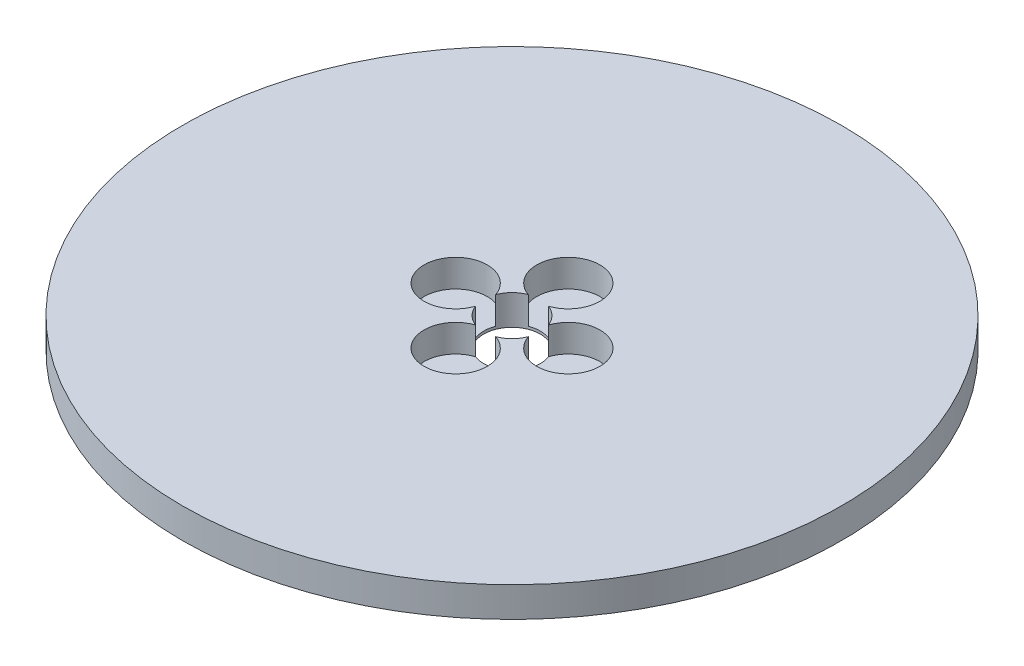
SolidWorks part; units mm, degrees
ref_plane "Front Plane" through (0, 0, 0) normal (0, 0, 1) x (1, 0, 0)
ref_plane "Top Plane" through (0, 0, 0) normal (0, 1, 0) x (1, 0, 0)
ref_plane "Right Plane" through (0, 0, 0) normal (1, 0, 0) x (0, 0, -1)
sketch "Sketch1" plane through (0, 0, 0) normal (0, 1, 0) x (1, 0, 0)
  circle A0 centre (0, 0) radius 87.5
  dimension "FLANGE_OD" = 175
extrude "Boss-Extrude1" add sketch "Sketch1" along normal blind 8
sketch "Sketch2" plane through (0, 0, 0) normal (0, 1, 0) x (1, 0, 0)
  circle A0 centre (0, 0) radius 7.5
  dimension "BORE_D" = 15
extrude "Cut-Extrude1" cut sketch "Sketch2" along normal through all
sketch "Sketch3" plane through (0, 8, 0) normal (0, 1, 0) x (1, 0, 0)
  circle A0 centre (0, 0) radius 14.9537 construction
  circle A1 centre (-14.9537, 0) radius 8.3883
  dimension "BOLT_D" = 16.7766
  dimension "BOLT_PCD" = 29.9073
extrude "Cut-Extrude2" cut sketch "Sketch3" against normal blind 7.2931
pattern_circular "CirPattern1" count 4 over 360 about axis through (0, 0, 0) along (0, 1, 0) of "Cut-Extrude2"
